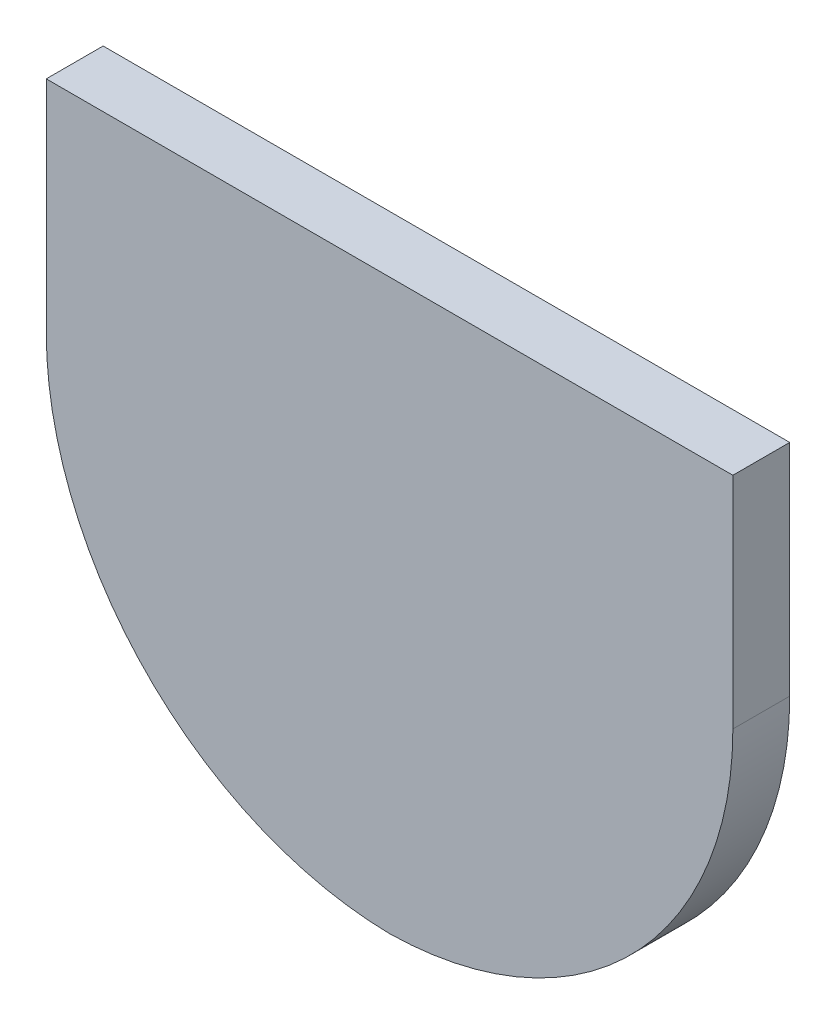
SolidWorks part; units mm, degrees
ref_plane "Спереди" through (0, 0, 0) normal (0, 0, 1) x (1, 0, 0)
ref_plane "Сверху" through (0, 0, 0) normal (0, 1, 0) x (1, 0, 0)
ref_plane "Справа" through (0, 0, 0) normal (1, 0, 0) x (0, 0, -1)
sketch "Эскиз1" plane through (0, 0, 0) normal (0, 0, 1) x (1, 0, 0)
  line L1 (-17.5334, 11.2) -> (9.0266, 11.2)
  line L2 (-17.5334, 11.2) -> (-17.5334, -10.8)
  line L3 (-17.5334, -10.8) -> (9.0266, -10.8)
  line L4 (9.0266, 11.2) -> (9.0266, -10.8)
  line L5 (-4.2534, -10.8) -> (-4.2534, 11.2) construction
  line L6 (-17.5334, 0.2) -> (9.0266, 0.2) construction
  point P0 (-4.2534, 0.2)
  dimension "D1" = 22
  dimension "D2" = 26.56
extrude "Бобышка-Вытянуть1" add sketch "Эскиз1" along normal blind 2.2
fillet "Скругление1" radius 13.5 2 edges at (9.0266, -10.8, 1.1) (-17.5334, -10.8, 1.1)
